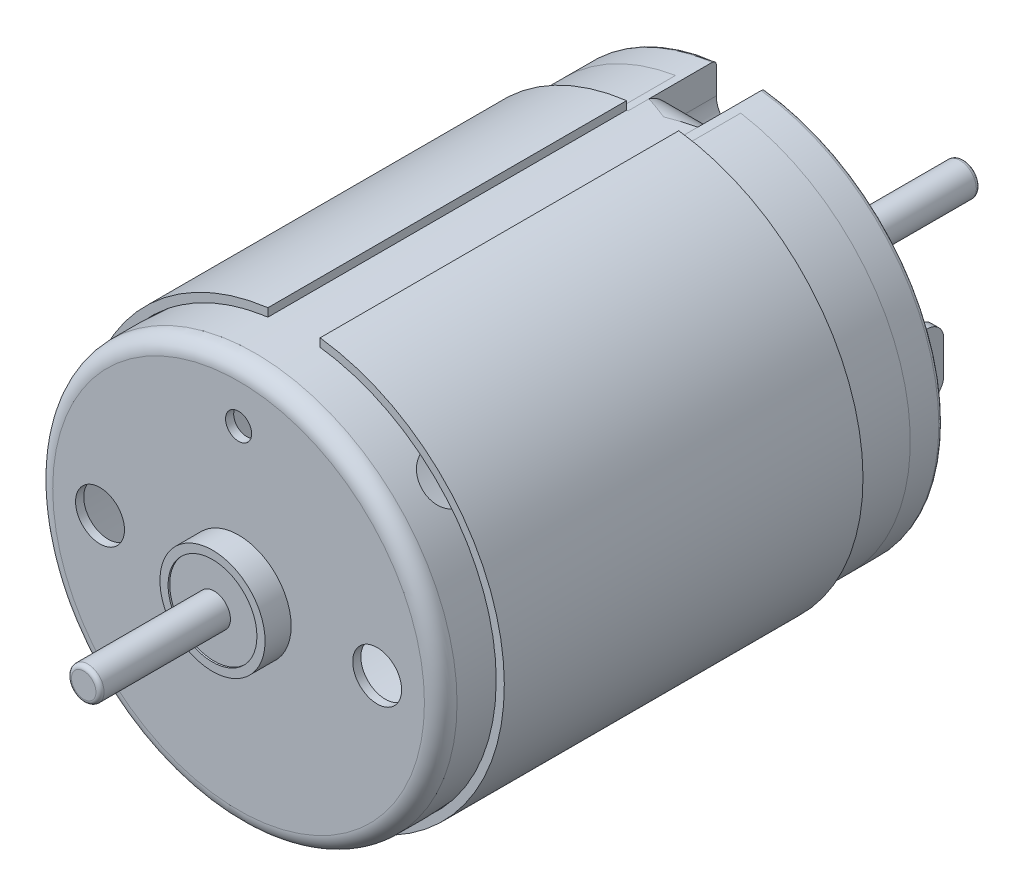
SolidWorks part; units mm, degrees
other "Camera1"
ref_plane "Ön Düzlem" through (0, 0, 0) normal (0, 0, 1) x (1, 0, 0)
ref_plane "Üst Düzlem" through (0, 0, 0) normal (0, 1, 0) x (1, 0, 0)
ref_plane "Sağ Düzlem" through (0, 0, 0) normal (1, 0, 0) x (0, 0, -1)
sketch "Sketch1" plane through (0, 0, 0) normal (0, 0, 1) x (1, 0, 0)
  circle A0 centre (0, 0) radius 12.4
  dimension "D1" = 24.8
extrude "Base" add sketch "Sketch1" along normal blind 28.8
sketch "Sketch2" plane through (0, 0, 0) normal (0, 0, -1) x (-1, 0, 0)
  circle A0 centre (0, 0) radius 12.4
extrude "Boss-Extrude2" add sketch "Sketch2" along normal blind 2 separate body
sketch "Sketch3" plane through (0, 0, -2) normal (0, 0, -1) x (-1, 0, 0)
  line L0 (-12.4, 0) -> (12.4, 0) construction
  line L1 (-1.4361, 4) -> (1.4361, 4)
  line L2 (-1.4361, -4) -> (1.4361, -4)
  arc A0 (-1.4361, 4) -> (-1.4361, -4) centre (0, 0) ccw
  circle A1 centre (0, 0) radius 12.4 construction
  arc A2 (1.4361, -4) -> (1.4361, 4) centre (0, 0) ccw
  circle A3 centre (0, 0) radius 1
  dimension "D1" = 8.5
  dimension "D4" = 2
  dimension "D2" = 8
  dimension "D3" = 4
extrude "Boss-Extrude3" add sketch "Sketch3" along normal blind 1.7
sketch "Sketch4" plane through (0, 0, -2) normal (0, 0, -1) x (-1, 0, 0)
  line L0 (-12.4, 0) -> (12.4, 0) construction
  line L1 (-2, 7.0711) -> (-2, 4.899)
  line L2 (6.7904, -4.2298) -> (9.5, -4.2298)
  line L3 (10, -3.7298) -> (10, 3.7298)
  line L4 (9.5, 4.2298) -> (6.7904, 4.2298)
  line L5 (-6.7904, 4.2298) -> (-9.5, 4.2298)
  line L6 (2, 7.0711) -> (2, 4.899)
  line L7 (-6.7904, -4.2298) -> (-9.5, -4.2298)
  line L8 (-10, 3.7298) -> (-10, -3.7298)
  line L9 (-2, -4.899) -> (-2, -7.0711)
  line L10 (2, -4.899) -> (2, -7.0711)
  line L11 (0, -12.4) -> (0, 12.4) construction
  line L12 (-2, -4.4536) -> (2, -4.4536) construction
  arc A0 (6.7904, 4.2298) -> (2.6667, 7.5425) centre (0, 0) ccw
  arc A1 (-6.7904, -4.2298) -> (-2.6667, -7.5425) centre (0, 0) ccw
  circle A2 centre (0, 0) radius 12.4 construction
  arc A3 (2.2727, -4.4536) -> (2.2727, 4.4536) centre (0, 0) ccw
  arc A4 (-2.6667, 7.5425) -> (-6.7904, 4.2298) centre (0, 0) ccw
  arc A5 (2.6667, -7.5425) -> (6.7904, -4.2298) centre (0, 0) ccw
  arc A6 (-2.2727, 4.4536) -> (-2.2727, -4.4536) centre (0, 0) ccw
  arc A7 (2, -7.0711) -> (2.6667, -7.5425) centre (2.5, -7.0711) ccw
  arc A8 (2, -4.899) -> (2.2727, -4.4536) centre (2.5, -4.899) cw
  arc A9 (-2, -4.899) -> (-2.2727, -4.4536) centre (-2.5, -4.899) ccw
  arc A10 (-2, -7.0711) -> (-2.6667, -7.5425) centre (-2.5, -7.0711) cw
  arc A11 (2, 4.899) -> (2.2727, 4.4536) centre (2.5, 4.899) ccw
  arc A12 (-2, 7.0711) -> (-2.6667, 7.5425) centre (-2.5, 7.0711) ccw
  arc A13 (-2, 4.899) -> (-2.2727, 4.4536) centre (-2.5, 4.899) cw
  arc A14 (2, 7.0711) -> (2.6667, 7.5425) centre (2.5, 7.0711) cw
  arc A15 (10, 3.7298) -> (9.5, 4.2298) centre (9.5, 3.7298) ccw
  arc A16 (9.5, -4.2298) -> (10, -3.7298) centre (9.5, -3.7298) ccw
  arc A17 (-9.5, -4.2298) -> (-10, -3.7298) centre (-9.5, -3.7298) cw
  arc A18 (-9.5, 4.2298) -> (-10, 3.7298) centre (-9.5, 3.7298) ccw
  circle A19 centre (0, -5.2036) radius 0.75
  circle A20 centre (0, 5.2036) radius 0.75
  point P25 (2, -7.746)
  point P34 (2, 4.5826)
  point P37 (-2, 7.746)
  point P40 (-2, 4.5826)
  dimension "D1" = 16
  dimension "D2" = 10
  dimension "D4" = 10
  dimension "D7" = 0.5
  dimension "D8" = 1.5
  dimension "D9" = 0.75
  dimension "D3" = 10
  dimension "D5" = 2
  dimension "D6" = 2
extrude "Cut-Extrude1" cut sketch "Sketch4" against normal blind 0.5
sketch "Sketch5" plane through (0, 0, -2) normal (0, 0, -1) x (-1, 0, 0)
  line L0 (0, 12.4) -> (0, -12.4) construction
  line L2 (-2, 12.2376) -> (-2, 10.4)
  line L3 (2, 10.4) -> (2, 12.2376)
  line L4 (-12.4, 0) -> (12.4, 0) construction
  line L5 (2, -10.4) -> (2, -12.2376)
  line L6 (-2, -12.2376) -> (-2, -10.4)
  circle A0 centre (0, 0) radius 12.4 construction
  arc A1 (-2, 10.4) -> (2, 10.4) centre (0, 10.4) ccw
  arc A2 (-2, 12.2376) -> (2, 12.2376) centre (0, 0) cw
  arc A3 (-2, -12.2376) -> (2, -12.2376) centre (0, 0) ccw
  arc A4 (-2, -10.4) -> (2, -10.4) centre (0, -10.4) cw
  dimension "D1" = 4
  dimension "D2" = 2
extrude "Cut-Extrude2" cut sketch "Sketch5" against normal blind 5.4
sketch "Sketch6" plane through (0, 0, -2) normal (0, 0, -1) x (-1, 0, 0)
  line L0 (-2, 10.4) -> (-2, 12.2376)
  line L1 (2, 10.4) -> (2, 12.2376)
  line L2 (-1.5, 10.4) -> (-1.5, 12.3089)
  line L3 (1.5, 10.4) -> (1.5, 12.3089)
  arc A0 (-2, 10.4) -> (2, 10.4) centre (0, 10.4) ccw
  arc A1 (-1.5, 10.4) -> (1.5, 10.4) centre (0, 10.4) ccw
  arc A2 (2, 12.2376) -> (-2, 12.2376) centre (0, 0) ccw construction
  arc A3 (-2, 12.2376) -> (-1.5, 12.3089) centre (0, 0) cw
  arc A4 (1.5, 12.3089) -> (2, 12.2376) centre (0, 0) cw
  dimension "D1" = 3
extrude "Boss-Extrude4" add sketch "Sketch6" against normal blind 5.4
sketch "Sketch7" plane through (0, 0, 3.4) normal (0, 0, -1) x (-1, 0, 0)
  line L0 (-1.5, 10.4) -> (-1.5, 11.553)
  line L1 (1.5, 10.4) -> (1.5, 11.553)
  arc A0 (-1.5, 10.4) -> (1.5, 10.4) centre (0, 10.4) ccw
  arc A2 (1.5, 11.553) -> (-1.5, 11.553) centre (0, 0) ccw
extrude "Boss-Extrude5" add sketch "Sketch7" along normal blind 1
mirror "Mirror1" about plane through (0, 0, 0) normal (0, 1, 0) of "Boss-Extrude5", "Boss-Extrude4"
sketch "Sketch11" plane through (0, 0, 0) normal (1, 0, 0) x (0, 0, -1)
  line L0 (-3.4, 12.4) -> (-2.7284, 12.4)
  line L1 (-3.4, 12.4) -> (-3.4, 11.65)
  line L2 (-3.4, 12.2376) -> (-3.4, 12.4) construction
  line L3 (-3.4, 11.65) -> (-3.0391, 11.65)
  line L4 (-3.4, 11.65) -> (-3.4, 11.553) construction
  line L5 (-3.4, 12.3089) -> (-3.4, 11.553) construction
  line L6 (-1.6249, 11.0642) -> (-0.309, 9.7483)
  line L7 (-0.309, 9.7483) -> (0.2213, 10.2787)
  line L8 (0.2213, 10.2787) -> (-1.3142, 11.8142)
  arc A0 (-1.6249, 11.0642) -> (-3.0391, 11.65) centre (-3.0391, 9.65) ccw
  arc A1 (-1.3142, 11.8142) -> (-2.7284, 12.4) centre (-2.7284, 10.4) ccw
  point P16 (-1.9, 12.4)
  dimension "D4" = 2
  dimension "D5" = 2
  dimension "D1" = 1.5
  dimension "D2" = 0.75
  dimension "D3" = 3
extrude "Boss-Extrude15" add sketch "Sketch11" against normal mid plane 3
sketch "Sketch14" plane through (0, 0, 28.8) normal (0, 0, 1) x (1, 0, 0)
  circle A0 centre (0, 0) radius 12.4
  circle A1 centre (0, 0) radius 13.3848
extrude "Cut-Extrude3" cut sketch "Sketch14" against normal through all
fillet "Fillet2" radius 1 2 edges at (1.5, 10.0135, 0.0438) (-1.5, 10.0135, 0.0438)
mirror "Mirror2" about plane through (0, 0, 0) normal (0, 1, 0) of "Fillet2", "Cut-Extrude3", "Boss-Extrude15"
sketch "Sketch15" plane through (0, 0, -1.5) normal (0, 0, -1) x (-1, 0, 0)
  line L0 (-12.4, 0) -> (12.4, 0) construction
  line L1 (-8.95, 2) -> (-8.45, 2)
  line L2 (-8.95, 2) -> (-8.95, -2)
  line L3 (-8.95, -2) -> (-8.45, -2)
  line L4 (-8.45, 2) -> (-8.45, -2)
  line L5 (0, 12.4) -> (0, -12.4) construction
  line L6 (8.45, 2) -> (8.45, -2)
  line L7 (8.95, -2) -> (8.45, -2)
  line L8 (8.95, 2) -> (8.95, -2)
  line L9 (8.95, 2) -> (8.45, 2)
  arc A1 (-1.5, 12.3089) -> (-1.5, -12.3089) centre (0, 0) ccw construction
  arc A2 (1.5, -12.3089) -> (1.5, 12.3089) centre (0, 0) ccw construction
  dimension "D1" = 0.5
  dimension "D2" = 4
  dimension "D3" = 2
  dimension "D4" = 16.9
extrude "Boss-Extrude16" add sketch "Sketch15" along normal blind 4
sketch "Sketch16" plane through (8.95, 0, 0) normal (1, 0, 0) x (0, 0, -1)
  line L0 (5.5, 2) -> (1.5, 2) construction
  line L1 (5.5, 2) -> (5.5, -2) construction
  circle A0 centre (3.5, 0) radius 0.75
  dimension "D1" = 1.5
  dimension "D2" = 2
  dimension "D3" = 2
extrude "Cut-Extrude4" cut sketch "Sketch16" against normal up to next (0.5 mm away)
fillet "Fillet3" radius 1 4 edges at (-8.7, -2, -5.5) (-8.7, 2, -5.5) (8.7, -2, -5.5) (8.7, 2, -5.5)
mirror "Mirror3" about plane through (0, 0, 0) normal (1, 0, 0) of "Cut-Extrude4"
sketch "Sketch17" plane through (0, 0, -2) normal (0, 0, -1) x (-1, 0, 0)
  circle A0 centre (0, 0) radius 1
extrude "Encoder Shaft" add sketch "Sketch17" along normal blind 13.7 separate body
fillet "Fillet4" radius 1 1 edges at (12.4, 0, 28.8)
sketch "Sketch18" plane through (0, 0, 28.8) normal (0, 0, 1) x (1, 0, 0)
  circle A0 centre (0, 0) radius 3.225
  circle A1 centre (0, 0) radius 2.725
  dimension "D1" = 6.45
  dimension "D2" = 0.5
extrude "Boss-Extrude18" add sketch "Sketch18" along normal blind 1.6
sketch "Sketch19" plane through (0, 0, 28.8) normal (0, 0, 1) x (1, 0, 0)
  circle A0 centre (0, 0) radius 2.725
  circle A1 centre (0, 0) radius 1
  dimension "D1" = 2
extrude "Boss-Extrude19" add sketch "Sketch19" along normal blind 1.5 separate body
sketch "Sketch20" plane through (0, 0, 28.8) normal (0, 0, 1) x (1, 0, 0)
  line L0 (0, 12.4) -> (0, -12.4) construction
  line L1 (-12.5081, 0) -> (12.4, 0) construction
  circle A0 centre (0, 0) radius 12.4 construction
  circle A1 centre (0, 9) radius 0.8
  circle A2 centre (-8.5, 0) radius 1.5
  circle A3 centre (8.5, 0) radius 1.5
  dimension "D1" = 9
  dimension "D2" = 1.6
  dimension "D3" = 17
  dimension "D4" = 8.5
  dimension "D5" = 3
  dimension "D6" = 3
extrude "Cut-Extrude5" cut sketch "Sketch20" against normal blind 0.5
ref_plane "Plane2" through (0, 0, 28.3) normal (0, 0, 1) x (1, 0, 0)
sketch "Sketch21" plane through (0, 0, 28.3) normal (0, 0, 1) x (1, 0, 0)
  circle A0 centre (0, 0) radius 11.9
  circle A1 centre (0, 0) radius 12.4 construction
  dimension "D1" = 0.5
extrude "Cut-Extrude6" cut sketch "Sketch21" against normal blind 23.5
sketch "Sketch22" plane through (0, 0, 28.8) normal (0, 0, 1) x (1, 0, 0)
  circle A0 centre (0, 0) radius 1
extrude "Front Shaft" add sketch "Sketch22" along normal blind 9.5
ref_plane "Plane3" through (0, 0, 25.4) normal (0, 0, 1) x (1, 0, 0)
sketch "Sketch24" plane through (0, 0, 25.4) normal (0, 0, 1) x (1, 0, 0)
  circle A0 centre (0, 0) radius 12.4
  circle A1 centre (0, 0) radius 12.9
  dimension "D1" = 0.5
extrude "Boss-Extrude21" add sketch "Sketch24" against normal blind 22 separate body
sketch "Sketch25" plane through (0, 0, 25.4) normal (0, 0, 1) x (1, 0, 0)
  line L0 (0, 0) -> (0, 13.4456) construction
  line L1 (-1.6, 12.8004) -> (-1.6, 12.2963)
  line L2 (1.6, 12.8004) -> (1.6, 12.2963)
  arc A0 (-1.6, 12.8004) -> (1.6, 12.8004) centre (0, 0) cw
  circle A1 centre (0, 0) radius 12.9 construction
  arc A2 (-1.6, 12.2963) -> (1.6, 12.2963) centre (0, 0) cw
  circle A3 centre (0, 0) radius 12.4 construction
  dimension "D1" = 1.6
  dimension "D2" = 1.6
extrude "Cut-Extrude8" cut sketch "Sketch25" against normal up to next (22 mm away)
ref_plane "Plane4" through (0, 0, 0) normal (-0.7071, 0.7071, 0) x (0.7071, 0.7071, 0)
sketch "Sketch26" plane through (0, 0, 0) normal (-0.7071, 0.7071, 0) x (0.7071, 0.7071, 0)
  line L0 (-3.225, -28.8) -> (3.225, -28.8) construction
  circle A0 centre (0, -24.8) radius 1.5
  dimension "D2" = 3
  dimension "D1" = 4
extrude "Cut-Extrude11" cut sketch "Sketch26" against normal through all both and the other way through all
pattern_circular "CirPattern1" count 2 every 90 about axis through (0, 0, 38.3) along (0, 0, -1) of "Cut-Extrude11"
fillet "Fillet5" radius 0.25 2 edges at (-12.4, 0, -2) (12.4, 0, -2)
fillet "Fillet6" radius 0.25 1 edges at (1, 0, 38.3)
fillet "Fillet7" radius 0.25 1 edges at (-1, 0, -15.7)
